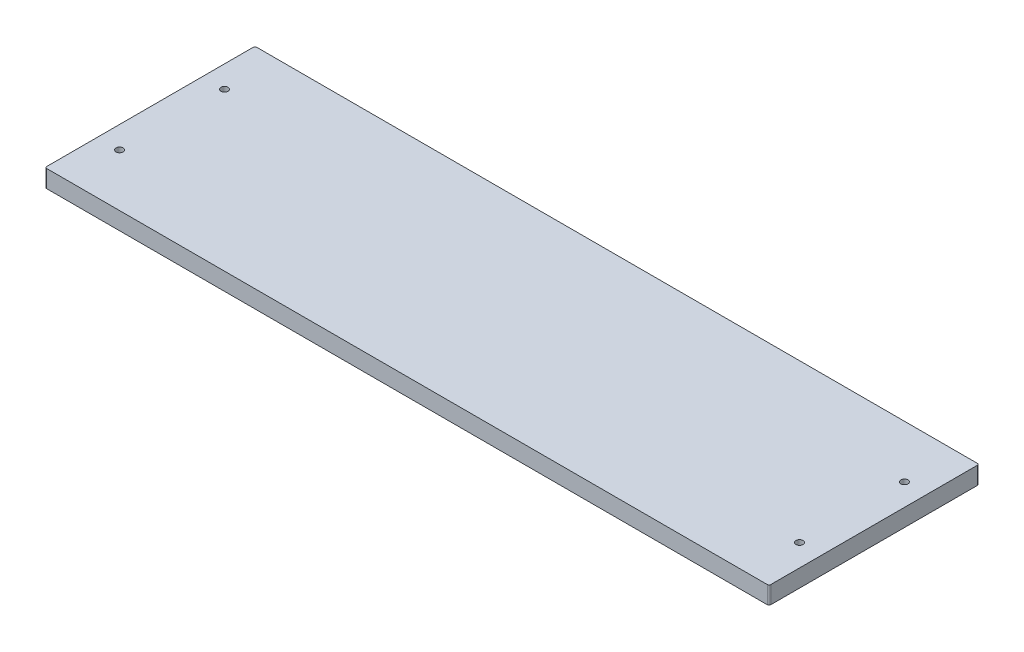
SolidWorks part; units mm, degrees
ref_plane "Front Plane" through (0, 0, 0) normal (0, 0, 1) x (1, 0, 0)
ref_plane "Top Plane" through (0, 0, 0) normal (0, 1, 0) x (1, 0, 0)
ref_plane "Right Plane" through (0, 0, 0) normal (1, 0, 0) x (0, 0, -1)
sketch "Sketch1" plane through (0, 0, 0) normal (0, 1, 0) x (1, 0, 0)
  line L1 (-262.7313, -76.2) -> (262.7312, -76.2)
  line L2 (-262.7313, -76.2) -> (-262.7313, 76.2)
  line L3 (-262.7313, 76.2) -> (262.7312, 76.2)
  line L4 (262.7312, -76.2) -> (262.7312, 76.2)
  line L5 (-262.7313, -76.2) -> (262.7312, 76.2) construction
  line L6 (-262.7313, 76.2) -> (262.7312, -76.2) construction
  point P0 (0, 0)
  dimension "D1" = 525.4625
  dimension "D2" = 152.4
extrude "Boss-Extrude1" add sketch "Sketch1" along normal blind 12.7
hole_wizard "#10 Clearance Hole1" positions "Sketch2" profile "Sketch3" hole size "#10" standard "ANSI Inch" end condition through all
sketch "Sketch2" plane through (0, 12.7, 0) normal (0, 1, 0) x (1, 0, 0)
  line L0 (-246.7293, 76.2) -> (-246.7293, -76.2) construction
  line L1 (262.7312, 76.2) -> (-262.7313, 76.2) construction
  line L2 (-262.7313, -76.2) -> (262.7312, -76.2) construction
  line L4 (246.7292, 76.2) -> (246.7292, -76.2) construction
  line L6 (-262.7313, 76.2) -> (-262.7313, -76.2) construction
  line L7 (262.7312, -76.2) -> (262.7312, 76.2) construction
  line L9 (-262.7313, 38.1) -> (262.7312, 38.1) construction
  line L11 (-262.7313, -38.1) -> (262.7312, -38.1) construction
  point P23 (-246.7293, 38.1)
  point P25 (-246.7293, -38.1)
  point P27 (246.7292, 38.1)
  point P29 (246.7292, -38.1)
  dimension "D1" = 16.002
  dimension "D2" = 16.002
  dimension "D3" = 38.1
  dimension "D4" = 38.1
sketch "Sketch3" plane through (246.7292, 12.7, 38.1) normal (1, 0, 0) x (0, 0, 1)
  line L0 (0, 0) -> (0, 12.7)
  line L1 (0, 12.7) -> (2.5527, 12.7)
  line L2 (2.5527, 12.7) -> (2.5527, 0)
  line L5 (2.5527, 0) -> (0, 0)
  line L11 (0, -6.35) -> (0, 107.95) construction
  dimension "Thru Hole Dia." = 5.1054
  dimension "Thru Hole Depth" = 12.7
fillet "Fillet1" radius 1.27 4 edges at (262.7312, 6.35, 76.2) (262.7312, 6.35, -76.2) (-262.7313, 6.35, 76.2) (-262.7313, 6.35, -76.2)
